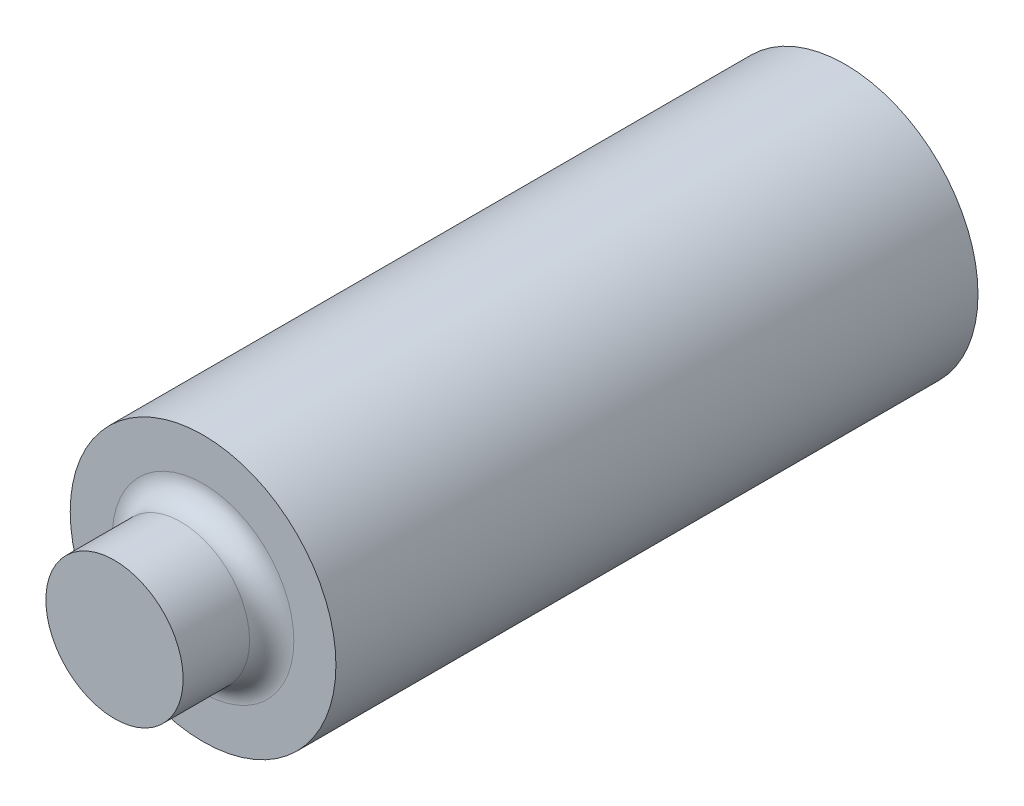
SolidWorks part; units mm, degrees
ref_plane "Front Plane" through (0, 0, 0) normal (0, 0, 1) x (1, 0, 0)
ref_plane "Top Plane" through (0, 0, 0) normal (0, 1, 0) x (1, 0, 0)
ref_plane "Right Plane" through (0, 0, 0) normal (1, 0, 0) x (0, 0, -1)
sketch "Sketch1" plane through (0, 0, 0) normal (0, 0, 1) x (1, 0, 0)
  circle A0 centre (0, 0) radius 1.55
  circle A1 centre (0, 0) radius 3
  dimension "D1" = 3.1
  dimension "D2" = 6
extrude "Boss-Extrude1" add sketch "Sketch1" along normal blind 14.5 contours A0 | A1 A0 region at (0, 0, 0) region at (-2.9151, 0, 0)
extrude "Boss-Extrude2" add sketch "Sketch1<3>" along normal blind 2 from surface contours A0 region at (0, 0, 0) starting at face at (3, 0, 14.5)
sketch "Sketch1<3>" plane through (0, 0, 0) normal (0, 0, 1) x (1, 0, 0) same geometry as "Sketch1"
fillet "Fillet1" radius 0.5 1 edges at (1.55, 0, 14.5)
